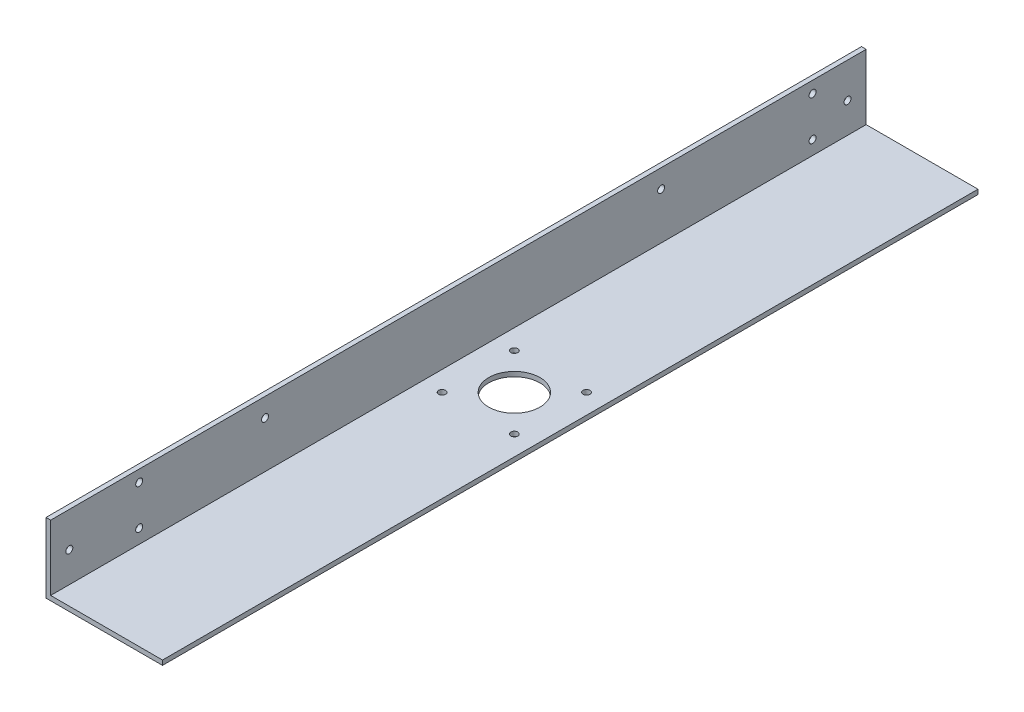
SolidWorks part; units mm, degrees
ref_plane "Front Plane" through (0, 0, 0) normal (0, 0, 1) x (1, 0, 0)
ref_plane "Top Plane" through (0, 0, 0) normal (0, 1, 0) x (1, 0, 0)
ref_plane "Right Plane" through (0, 0, 0) normal (1, 0, 0) x (0, 0, -1)
sketch "Sketch1" plane through (0, 0, 0) normal (0, 0, 1) x (1, 0, 0)
  line L0 (0, 0) -> (0, 30)
  line L1 (0, 30) -> (2, 30)
  line L2 (2, 30) -> (2, 2)
  line L3 (2, 2) -> (50, 2)
  line L4 (50, 2) -> (50, 0)
  line L5 (50, 0) -> (0, 0)
extrude "Boss-Extrude1" add sketch "Sketch1" along normal up to surface (350 mm away)
sketch "Sketch7" plane through (0, 2, 0) normal (0, 1, 0) x (1, 0, 0)
  circle A0 centre (26, -175) radius 11
  point P7 (2, -350)
extrude "Cut-Extrude1" cut sketch "Sketch7" against normal through all from surface starting at face at (26, 2, 175)
sketch "Sketch8" plane through (0, 2, 0) normal (0, 1, 0) x (1, 0, 0)
  circle A0 centre (41.5, -190.5) radius 1.5
  circle A1 centre (41.5, -159.5) radius 1.5
  circle A2 centre (10.5, -190.5) radius 1.5
  circle A3 centre (10.5, -159.5) radius 1.5
extrude "Cut-Extrude2" cut sketch "Sketch8" against normal through all
hole_wizard "Ø3.0 (3) Diameter Hole1" positions "Sketch9" profile "Sketch10" hole size "Ø3.0" standard "ISO"
sketch "Sketch9" plane through (0, 182.32, 128.862) normal (-1, 0, 0) x (0, 0, -1)
  point P0 (105.862, 174.32)
  point P2 (105.862, 157.32)
  point P4 (120.862, 167.32)
sketch "Sketch10" plane through (0, 8, 23) normal (0, 1, 0) x (0, 0, 1)
  line L0 (0, 0) -> (0, 1.999)
  line L1 (0, 1.999) -> (1.5, 1.999)
  line L2 (1.5, 1.999) -> (1.5, 0)
  line L3 (1.5, 0) -> (0, 0)
  line L4 (0, -6.35) -> (0, 107.95) construction
  dimension "Thru Hole Dia." = 3
  dimension "Thru Hole Depth" = 1.999
hole_wizard "Ø3.0mm Dowel Hole1" positions "Sketch13" profile "Sketch14" hole
sketch "Sketch13" plane through (0, 182.32, 128.862) normal (-1, 0, 0) x (0, 0, -1)
  point P0 (-183.138, 157.32)
  point P1 (-213.138, 167.32)
  point P2 (-183.138, 174.32)
sketch "Sketch14" plane through (0, 25, 312) normal (0, 1, 0) x (0, 0, 1)
  line L0 (0, 0) -> (0, 1.999)
  line L1 (0, 1.999) -> (1.5, 1.999)
  line L2 (1.5, 1.999) -> (1.5, 0)
  line L3 (1.5, 0) -> (0, 0)
  line L4 (0, -6.35) -> (0, 107.95) construction
  dimension "Thru Hole Dia." = 3
  dimension "Thru Hole Depth" = 1.999
sketch "Sketch15" plane through (0, 0, 0) normal (-1, 0, 0) x (0, 0, 1)
  circle A0 centre (88, 22) radius 1.5
  circle A1 centre (258, 22) radius 1.5
extrude "Cut-Extrude3" cut sketch "Sketch15" against normal through all
